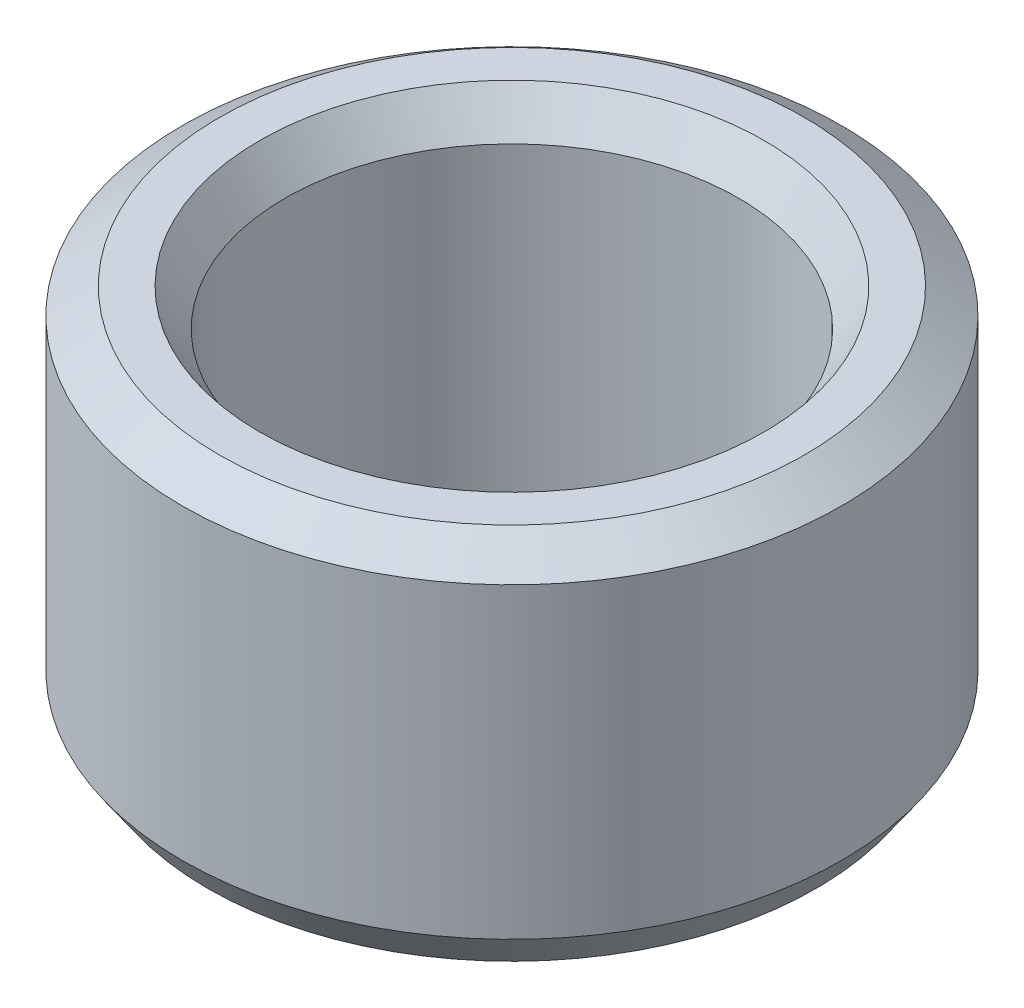
SolidWorks part; units mm, degrees
ref_plane "Front Plane" through (0, 0, 0) normal (0, 0, 1) x (1, 0, 0)
ref_plane "Top Plane" through (0, 0, 0) normal (0, 1, 0) x (1, 0, 0)
ref_plane "Right Plane" through (0, 0, 0) normal (1, 0, 0) x (0, 0, -1)
sketch "Sketch1" plane through (0, 0, 0) normal (0, 1, 0) x (1, 0, 0)
  circle A0 centre (0, 0) radius 47.5
  dimension "SLEEVE_OD" = 95
extrude "Boss-Extrude1" add sketch "Sketch1" along normal blind 53.2834
sketch "Sketch2" plane through (0, 0, 0) normal (0, 1, 0) x (1, 0, 0)
  circle A0 centre (0, 0) radius 32.6884
  dimension "BORE_D" = 65.3769
extrude "Cut-Extrude1" cut sketch "Sketch2" along normal through all
chamfer "Chamfer1" distance 3.6864 angle 55.418 4 edges at (0, 53.2834, 32.6884) (0, 0, 32.6884) (0, 0, 47.5) (0, 53.2834, 47.5) first distance on face at (0, 53.2834, 32.6884) first distance on face at (0, 0, 32.6884) first distance on face at (0, 53.2834, 47.5)
